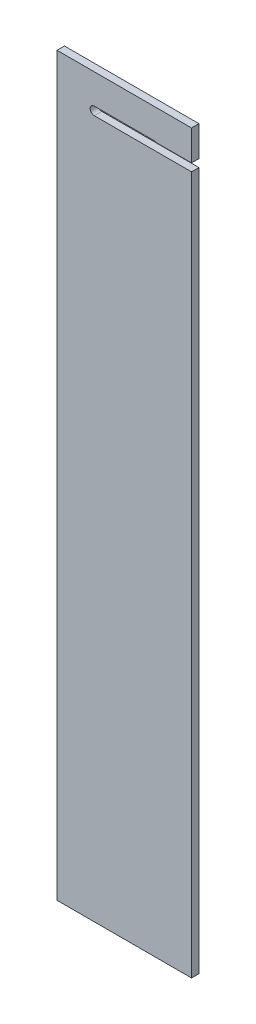
SolidWorks part; units mm, degrees
ref_plane "Front Plane" through (0, 0, 0) normal (0, 0, 1) x (1, 0, 0)
ref_plane "Top Plane" through (0, 0, 0) normal (0, 1, 0) x (1, 0, 0)
ref_plane "Right Plane" through (0, 0, 0) normal (1, 0, 0) x (0, 0, -1)
sketch "Sketch1" plane through (0, 0, 0) normal (0, 0, 1) x (1, 0, 0)
  line L0 (0, 149.225) -> (0, -149.225) construction
  line L1 (-28.75, 149.225) -> (28.75, 149.225)
  line L2 (-28.75, 149.225) -> (-28.75, -149.225)
  line L3 (-28.75, -149.225) -> (28.75, -149.225)
  line L4 (28.75, 149.225) -> (28.75, -149.225)
  line L5 (28.75, 152.527) -> (12.827, 152.527)
  line L10 (0, 149.225) -> (0, 165.481) construction
  line L11 (12.827, 152.527) -> (12.827, 152.781)
  line L12 (-28.75, 149.225) -> (28.75, 149.225)
  line L13 (-28.75, 149.225) -> (-28.75, 165.481)
  line L14 (-28.75, 165.481) -> (28.75, 165.481)
  line L15 (28.75, 149.225) -> (28.75, 165.481)
  line L16 (12.827, 152.781) -> (-12.827, 152.781)
  line L17 (-12.827, 152.781) -> (-12.827, 149.225)
  arc A0 (-12.827, 152.781) -> (-12.827, 149.225) centre (-12.827, 151.003) ccw
  point P6 (0, 0)
  point P21 (0, 152.781)
  dimension "D3" = 12.7
  dimension "D1" = 298.45
  dimension "D2" = 57.5
  dimension "D4" = 0.254
  dimension "D5" = 3.302
  dimension "D6" = 25.654
extrude "Boss-Extrude1" add sketch "Sketch1" along normal blind 3.175 contours L4 L12 L1 L2 L3 | L17 L16 L11 L5 L15 L14 L13 L1 region at (-1.3049, 158.5635, 0) region at (0, 0, 0)
fillet "Fillet1" radius 3.175 1 edges at (12.827, 152.527, 1.5875)
equation "\"Height\"= 12in"
equation "\"Depth\"= 7in"
equation "\"WallThickness\"= 0.125in"
equation "\"FloorThickness\"= 0.25in"
equation "\"Width\" = 30in"
equation "\"D1@Boss-Extrude1\"=\"WallThickness\""
